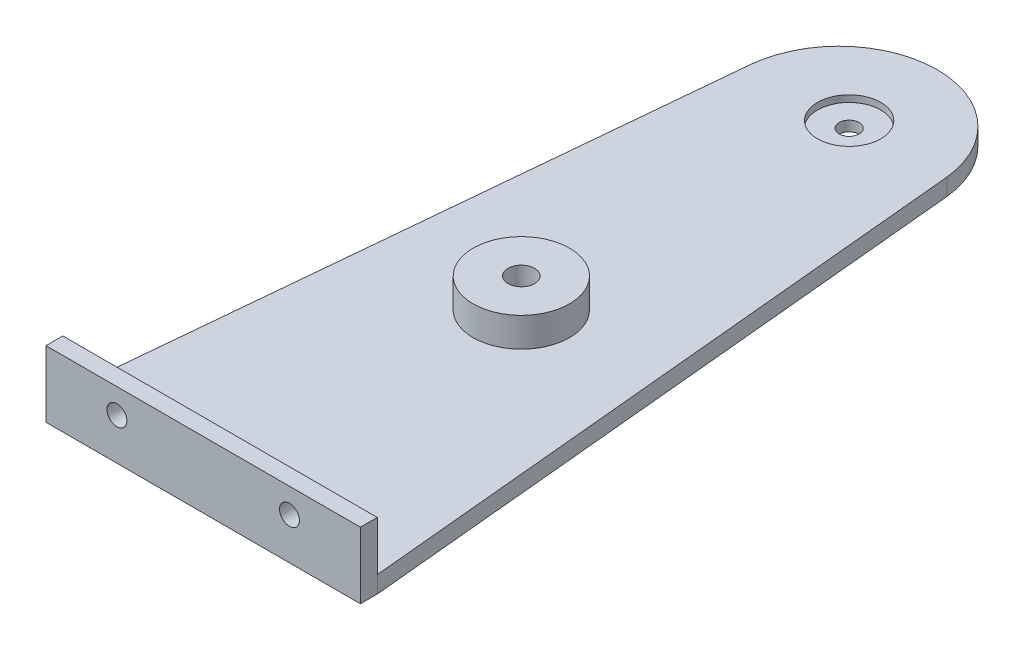
SolidWorks part; units mm, degrees
note: The reader was unsure of these and kept them because the rebuilt part matched: shared geometry of "Sketch2<5>", "Sketch2<6>", "Sketch2<7>".
ref_plane "Front Plane" through (0, 0, 0) normal (0, 0, 1) x (1, 0, 0)
ref_plane "Top Plane" through (0, 0, 0) normal (0, 1, 0) x (1, 0, 0)
ref_plane "Right Plane" through (0, 0, 0) normal (1, 0, 0) x (0, 0, -1)
sketch "Sketch2" plane through (0, 0, 0) normal (0, -1, 0) x (1, 0, 0)
  line L0 (-0.0202, 0) -> (0, 57.1196) construction
  line L5 (-0.0202, 46.4243) -> (-0.0202, 0) construction
  line L6 (14.7185, 0) -> (23.6804, 94.809)
  line L8 (-0.0202, 46.4243) -> (-0.0202, 94.809) construction
  line L9 (23.6804, 94.809) -> (-0.0202, 94.809) construction
  line L11 (9.8858, 9.7213) -> (-9.9262, 9.7213) construction
  line L12 (-14.7589, 0) -> (14.7185, 0) construction
  line L13 (-14.7589, 0) -> (-23.7006, 94.809)
  line L14 (23.6804, 94.809) -> (-23.7006, 94.809) construction
  line L15 (23.6804, 94.809) -> (-23.7006, 94.809)
  line L16 (23.6804, 94.809) -> (23.6804, 96.809)
  line L17 (23.6804, 96.809) -> (-23.7006, 96.809)
  line L18 (-23.7006, 96.809) -> (-23.7006, 94.809)
  circle A0 centre (-0.0202, 0) radius 4.7625
  circle A1 centre (-0.0202, 0) radius 1.5
  circle A2 centre (-0.0202, 49.3983) radius 2
  arc A3 (14.7185, 0) -> (-14.7589, 0) centre (-0.0202, 1.5364) cw
  circle A4 centre (-0.0202, 49.3983) radius 7.268
  circle A5 centre (-0.0202, 0) radius 47.3983 construction
  circle A6 centre (-0.0202, 0) radius 51.3983 construction
  point P28 (-0.0202, 0)
extrude "Boss-Extrude3" add sketch "Sketch2" along normal blind 2.54
sketch "Sketch3" plane through (0, 0, 94.809) normal (0, 0, 1) x (1, 0, 0)
  line L0 (-23.7006, -2.54) -> (-23.7006, 7.46)
  line L1 (23.6804, -2.54) -> (23.6804, 7.46)
  line L2 (23.6804, 7.46) -> (-23.7006, 7.46)
  line L3 (23.6804, -2.54) -> (-23.7006, -2.54)
  line L4 (-13.0101, 3.73) -> (12.9899, 3.73) construction
  line L5 (-0.0101, 3.73) -> (-0.0101, -2.54) construction
  circle A4 centre (-13.0101, 3.73) radius 1.5
  circle A5 centre (12.9899, 3.73) radius 1.5
extrude "Boss-Extrude6" add sketch "Sketch3" along normal blind 2.54
extrude "Cut-Extrude1" cut sketch "Sketch2<5>" along normal blind 10 contours A1
sketch "Sketch2<5>" plane through (0, 0, 0) normal (0, -1, 0) x (1, 0, 0) same geometry as "Sketch2"
extrude "Cut-Extrude2" cut sketch "Sketch2<6>" along normal blind 1 contours A0 A1
sketch "Sketch2<6>" plane through (0, 0, 0) normal (0, -1, 0) x (1, 0, 0) same geometry as "Sketch2"
extrude "Boss-Extrude7" add sketch "Sketch2<7>" against normal blind 4.4201 contours A4 A2
sketch "Sketch2<7>" plane through (0, 0, 0) normal (0, -1, 0) x (1, 0, 0) same geometry as "Sketch2"
